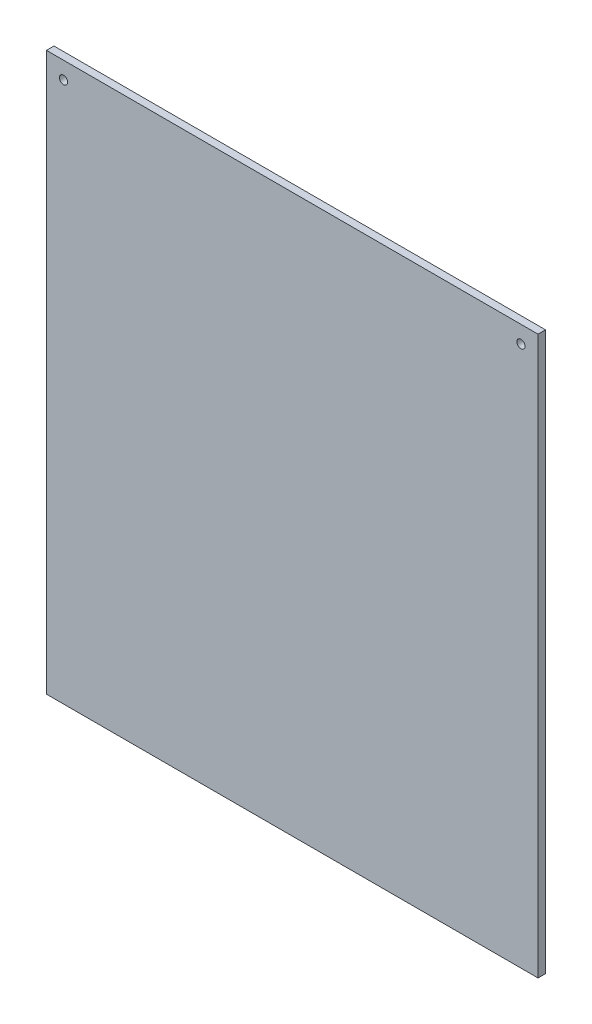
SolidWorks part; units mm, degrees
ref_plane "Front Plane" through (0, 0, 0) normal (0, 0, 1) x (1, 0, 0)
ref_plane "Top Plane" through (0, 0, 0) normal (0, 1, 0) x (1, 0, 0)
ref_plane "Right Plane" through (0, 0, 0) normal (1, 0, 0) x (0, 0, -1)
sketch "Sketch1" plane through (0, 0, 0) normal (0, 0, 1) x (1, 0, 0)
  line L0 (81.8848, 124.8822) -> (81.8848, -120.1178)
  line L1 (81.8848, 124.8822) -> (-134.1152, 124.8822)
  line L2 (81.8848, -120.1178) -> (-134.1152, -120.1178)
  line L3 (-134.1152, 124.8822) -> (-134.1152, -120.1178)
  circle A0 centre (-126.6152, 117.3822) radius 1.8
  circle A1 centre (74.3848, 117.3822) radius 1.8
  dimension "D3" = 7.5
  dimension "D1" = 245
  dimension "D2" = 216
  dimension "D4" = 7.5
  dimension "D5" = 7.5
  dimension "D6" = 7.5
extrude "Boss-Extrude1" add sketch "Sketch1" along normal blind 3.302
